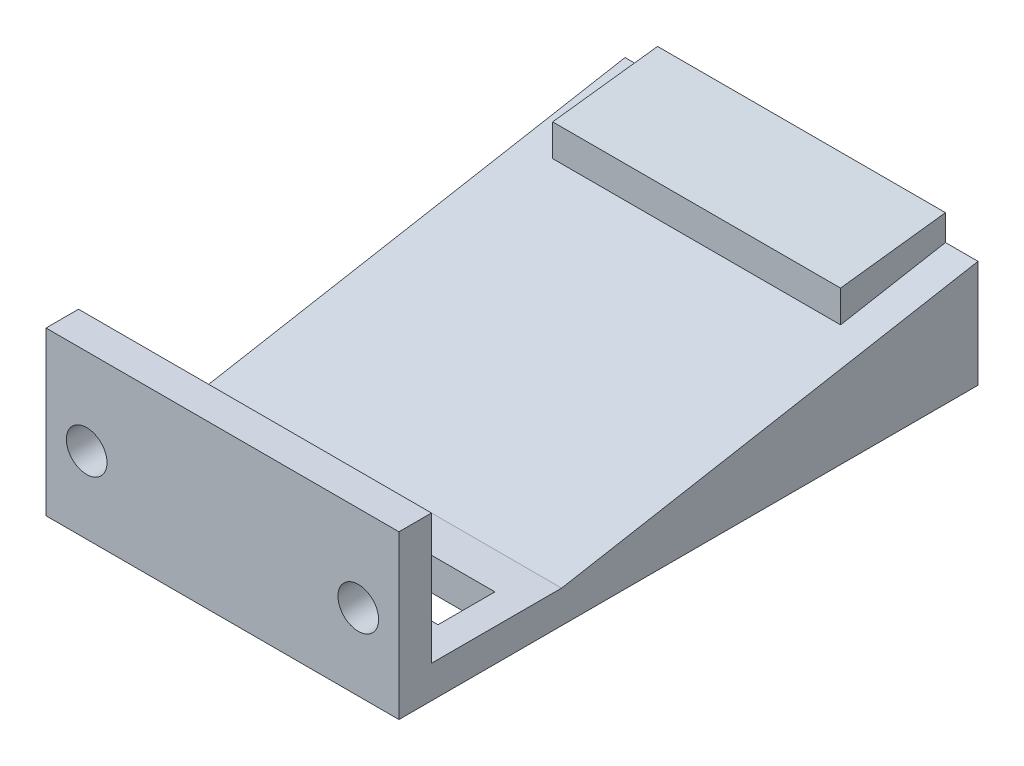
SolidWorks part; units mm, degrees
ref_plane "Front Plane" through (0, 0, 0) normal (0, 0, 1) x (1, 0, 0)
ref_plane "Top Plane" through (0, 0, 0) normal (0, 1, 0) x (1, 0, 0)
ref_plane "Right Plane" through (0, 0, 0) normal (1, 0, 0) x (0, 0, -1)
sketch "Sketch1" plane through (0, 0, 0) normal (0, 1, 0) x (1, 0, 0)
  line L1 (-10.85, 16.8) -> (10.85, 16.8)
  line L2 (-10.85, 16.8) -> (-10.85, -16.8)
  line L3 (-10.85, -16.8) -> (10.85, -16.8)
  line L4 (10.85, 16.8) -> (10.85, -16.8)
  line L5 (-10.85, 16.8) -> (10.85, -16.8) construction
  line L6 (-10.85, -16.8) -> (10.85, 16.8) construction
  point P0 (0, 0)
  dimension "D1" = 21.7
  dimension "D2" = 33.6
extrude "Boss-Extrude1" add sketch "Sketch1" along normal blind 3
sketch "Sketch2" plane through (0, 3, 0) normal (0, 1, 0) x (1, 0, 0)
  line L0 (-10.85, -16.8) -> (10.85, -16.8) construction
  line L1 (-9, -11.05) -> (9, -11.05)
  line L2 (-9, -11.05) -> (-9, -14.55)
  line L3 (-9, -14.55) -> (9, -14.55)
  line L4 (9, -11.05) -> (9, -14.55)
  line L5 (-9, -11.05) -> (9, -14.55) construction
  line L6 (-9, -14.55) -> (9, -11.05) construction
  point P0 (0, -12.8)
  point P9 (0, -16.8)
  dimension "D1" = 3.5
  dimension "D2" = 18
  dimension "D3" = 4
extrude "Cut-Extrude1" cut sketch "Sketch2" against normal blind 2
sketch "Sketch3" plane through (10.85, 0, 0) normal (1, 0, 0) x (0, 0, -1)
  line L0 (-8.8, 3) -> (16.8, 7.6)
  line L1 (-16.8, 3) -> (16.8, 3) construction
  line L2 (16.8, 7.6) -> (16.8, 3)
  line L3 (16.8, 3) -> (-8.8, 3)
  dimension "D1" = 8
  dimension "D2" = 4.6
extrude "Boss-Extrude2" add sketch "Sketch3" against normal up to surface (21.7 mm away) up to face at (-10.85, 1.5, 0)
sketch "Sketch4" plane through (0, 0, 0.2732) normal (0, 1, 0) x (1, 0, 0)
  line L0 (10.85, 17.0732) -> (10.85, -8.5268) construction
  line L1 (-8.85, 17.0732) -> (8.85, 17.0732)
  line L2 (-8.85, 17.0732) -> (-8.85, 10.6232)
  line L3 (-8.85, 10.6232) -> (8.85, 10.6232)
  line L4 (8.85, 17.0732) -> (8.85, 10.6232)
  line L5 (-8.85, 17.0732) -> (8.85, 10.6232) construction
  line L6 (-8.85, 10.6232) -> (8.85, 17.0732) construction
  line L7 (-10.85, -8.5268) -> (-10.85, 17.0732) construction
  line L8 (-10.85, 17.0732) -> (10.85, 17.0732) construction
  point P0 (0, 13.8482)
  dimension "D1" = 2
  dimension "D2" = 2
  dimension "D3" = 6.45
extrude "Boss-Extrude3" add sketch "Sketch4" along normal blind 9.2
sketch "Sketch5" plane through (0, 0, 0) normal (0, 1, 0) x (1, 0, 0)
  line L0 (-10.85, -16.8) -> (10.85, -16.8) construction
  line L2 (-10.85, -16.8) -> (-10.85, -18.8)
  line L3 (-10.85, -18.8) -> (10.85, -18.8)
  line L4 (10.85, -16.8) -> (10.85, -18.8)
  line L5 (0, -16.8) -> (10.85, -18.8) construction
  line L6 (-10.85, -18.8) -> (0, -16.8) construction
  line L7 (-10.85, -16.8) -> (10.85, -16.8)
  point P0 (0, -16.8)
  dimension "D1" = 2
extrude "Boss-Extrude4" add sketch "Sketch5" along normal blind 11
hole_wizard "Ø1.0mm Dowel Hole1" positions "Sketch6" profile "Sketch7" hole size "Ø1.0" standard "ANSI Metric"
sketch "Sketch6" plane through (0, 0, 18.8) normal (0, 0, 1) x (1, 0, 0)
  line L0 (-10.85, 0) -> (10.85, 0) construction
  line L1 (-10.85, 11) -> (-10.85, 0) construction
  line L2 (10.85, 11) -> (10.85, 0) construction
  point P0 (-8.35, 5.7)
  point P2 (8.35, 5.7)
  dimension "D1" = 5.7
  dimension "D2" = 2.5
  dimension "D3" = 2.5
sketch "Sketch7" plane through (-8.35, 5.7, 18.8) normal (1, 0, 0) x (0, -1, 0)
  line L0 (0, 0) -> (0, 10)
  line L1 (0, 10) -> (1.25, 9.2489)
  line L2 (1.25, 9.2489) -> (1.25, 0)
  line L5 (1.25, 0) -> (0, 0)
  line L10 (0, 10) -> (-1.25, 9.2489) construction
  line L11 (0, -6.35) -> (0, 107.95) construction
  dimension "Hole Dia." = 2.5
  dimension "Hole Depth" = 10
  dimension "Drill Angle" = 118
chamfer "Chamfer1" distance 0.8 angle 83 1 edges at (0, 9.2, -10.35) first distance on face at (0, 7.8205, -10.35)
sketch "Sketch8" plane through (0, 0, 0) normal (0, -1, 0) x (1, 0, 0)
  line L4 (-10.85, 18.8) -> (-10.85, -16.8)
  line L5 (-10.85, -16.8) -> (10.85, -16.8)
  line L6 (10.85, -16.8) -> (10.85, 18.8)
  line L7 (10.85, 18.8) -> (-10.85, 18.8)
  line L8 (-10.85, 18.8) -> (-10.85, -16.8)
  line L9 (-10.85, -16.8) -> (10.85, -16.8)
  line L10 (10.85, -16.8) -> (10.85, 18.8)
  line L11 (10.85, 18.8) -> (-10.85, 18.8)
  dimension "D1" = 0
extrude "Cut-Extrude2" cut sketch "Sketch8" against normal blind 1 and the other way through all
